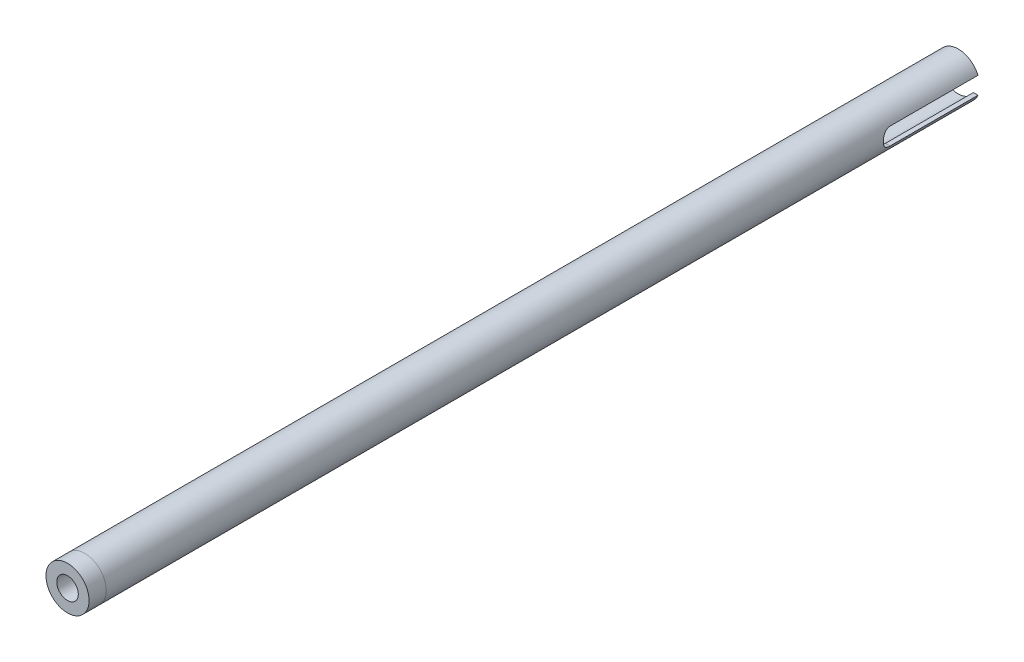
SolidWorks part; units mm, degrees
material "AISI 4130 Steel, annealed at 865C"
ref_plane "Front Plane" through (0, 0, 0) normal (0, 0, 1) x (1, 0, 0)
ref_plane "Top Plane" through (0, 0, 0) normal (0, 1, 0) x (1, 0, 0)
ref_plane "Right Plane" through (0, 0, 0) normal (1, 0, 0) x (0, 0, -1)
sketch "Axis" plane through (0, 0, 0) normal (0, 1, 0) x (1, 0, 0)
  line L0 (0, 0) -> (0, 328.0702) construction
  line L1 (0, 0) -> (0, -28.575) construction
  line L2 (0, 328.0702) -> (-7.9375, 328.0702) construction
  line L4 (0, 356.4735) -> (-26.4371, 261.8721) construction
  point P3 (-7.9375, 327.844)
  dimension "D1" = 28.575
  dimension "D2" = 7.9375
sketch "Sketch1" plane through (0, 0, 0) normal (0, 0, 1) x (1, 0, 0)
  line L0 (-7.9375, 0) -> (7.9375, 0) construction
  line L1 (-7.2748, 3.175) -> (7.2748, 3.175)
  line L2 (-7.2748, -3.175) -> (7.2748, -3.175)
  circle A0 centre (0, 0) radius 7.9375
  circle A1 centre (0, 0) radius 6.4135
  circle A2 centre (0, 0) radius 3.9688
  dimension "D1" = 15.875
  dimension "D3" = 7.9375
  dimension "D2" = 1.524
  dimension "D4" = 6.35
extrude "Threaded insert 1-1" add sketch "Sketch1" against normal blind 6.35 contours A2 L1 A1 | A1 L1 A0 | A2 L0 A1 L1 | A1 L0 A0 L1 | L0 A1 L2 A0 | L0 A2 L2 A1 | A2 L2 A1 | A1 L2 A0 | L0 A1 L2 A2 | L0 A0 L2 A1 | A0 L0 A1 L1 | A1 L0 A2 L1 region at (4.7887, 1.6543, 0) region at (4.7887, -1.6543, 0) region at (6.9234, 1.6163, 0) region at (6.9234, -1.6163, 0) region at (-4.7887, -1.6543, 0) region at (-4.7887, 1.6543, 0) region at (0, 4.6159, 0) region at (0, -4.6159, 0) region at (0, 6.5666, 0) region at (6.4237, -3.3281, 0) region at (-6.9234, -1.6163, 0) region at (-6.9234, 1.6163, 0)
extrude "Threaded insert 1-2" add sketch "Sketch1<3>" against normal blind 9.525 from surface contours A2 L1 A1 | A2 L0 A1 L1 | L0 A2 L2 A1 | A2 L2 A1 | L0 A1 L2 A2 | A1 L0 A2 L1 region at (4.7887, 1.6543, 0) region at (4.7887, -1.6543, 0) region at (-4.7887, -1.6543, 0) region at (-4.7887, 1.6543, 0) region at (0, 4.6159, 0) region at (0, -4.6159, 0) starting at face at (7.9375, 0, -6.35)
sketch "Sketch1<3>" plane through (0, 0, 0) normal (0, 0, 1) x (1, 0, 0) same geometry as "Sketch1"
extrude "A-arm tube" add sketch "Sketch1<4>" against normal up to vertex (328.0702 mm away) from surface separate body contours A1 L1 A0 | A1 L0 A0 L1 | L0 A1 L2 A0 | A1 L2 A0 | L0 A0 L2 A1 | A0 L0 A1 L1 region at (6.9234, 1.6163, 0) region at (6.9234, -1.6163, 0) region at (0, 6.5666, 0) region at (6.4237, -3.3281, 0) region at (-6.9234, -1.6163, 0) region at (-6.9234, 1.6163, 0) up to point (0, 0, -328.0702) starting at face at (6.4135, 0, -6.35)
sketch "Sketch1<4>" plane through (0, 0, 0) normal (0, 0, 1) x (1, 0, 0) same geometry as "Sketch1"
extrude "Apex slot" cut sketch "Sketch1<5>" along normal blind 35.56 from surface contours A0 L0 A1 L1 | L0 A0 L2 A1 | A1 L0 A0 L1 | L0 A1 L2 A0 region at (6.9234, 1.6163, 0) region at (6.9234, -1.6163, 0) region at (-6.9234, -1.6163, 0) region at (-6.9234, 1.6163, 0) starting at face at (6.4135, 0, -328.0702)
sketch "Sketch1<5>" plane through (0, 0, 0) normal (0, 0, 1) x (1, 0, 0) same geometry as "Sketch1"
fillet "Fillet1" radius 3.175 4 edges at (-6.4237, 3.175, -292.5102) (-6.4237, -3.175, -292.5102) (6.4237, -3.175, -292.5102) (6.4237, 3.175, -292.5102)
equation "\"tube diameter\"= 5 / 8"
equation "\"tube thickness\"= .06"
equation "\"apex thickness\"= .25"
equation "\"tube slot\"= 1.4"
equation "\"D1@Sketch1\"=\"tube diameter\""
equation "\"D2@Sketch1\"=\"tube thickness\""
equation "\"threaded insert hole\"= .3125"
equation "\"D3@Sketch1\"=\"threaded insert hole\""
equation "\"D4@Sketch1\"=\"apex thickness\""
equation "\"D1@Apex slot\" = \"tube slot\""
equation "\"D1@Fillet1\"=\"apex thickness\"/2"
equation "\"D2@Axis\"=\"tube diameter\"/2"
